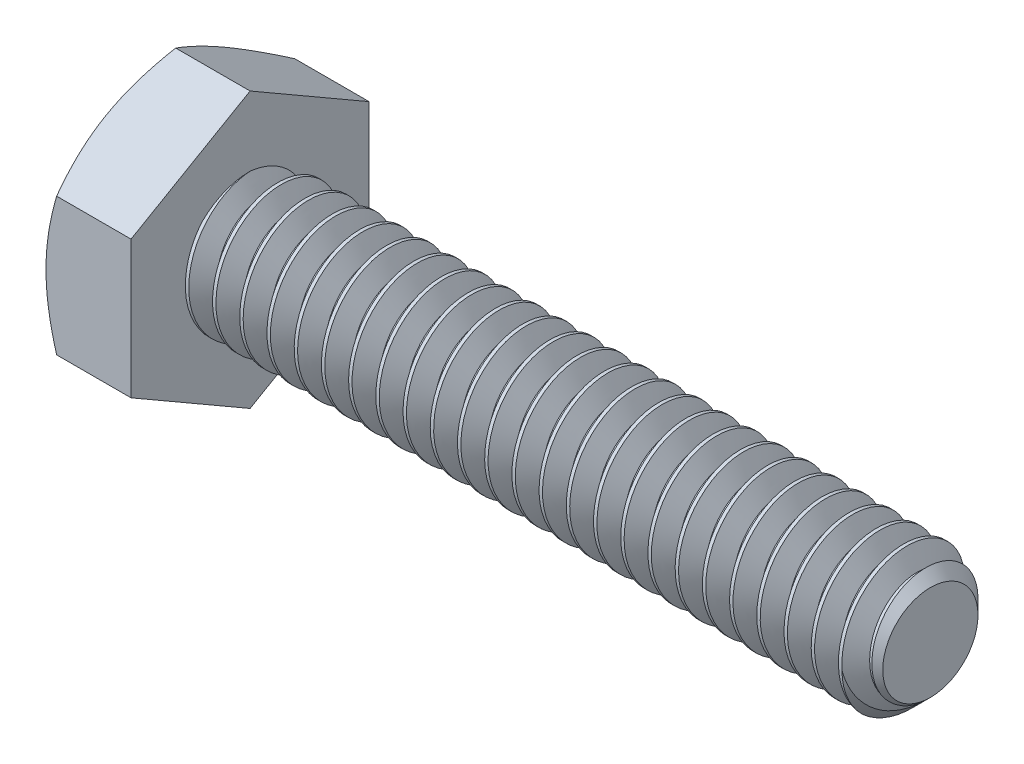
SolidWorks part; units mm, degrees
material "AISI 304"
ref_plane "Front Plane" through (0, 0, 0) normal (0, 0, 1) x (1, 0, 0)
ref_plane "Top Plane" through (0, 0, 0) normal (0, 1, 0) x (1, 0, 0)
ref_plane "Right Plane" through (0, 0, 0) normal (1, 0, 0) x (0, 0, -1)
sketch "Sketch1" plane through (0, 0, 0) normal (0, 0, 1) x (1, 0, 0)
  line L0 (-17.8594, 0) -> (17.8594, 0) construction
  line L1 (17.8594, 3.175) -> (17.8594, -3.175) construction
  line L2 (-13.8906, 5.5562) -> (-13.8906, -5.5562) construction
  line L3 (-17.8594, 5.5562) -> (-17.8594, -5.5562) construction
  point P9 (-13.8906, 0)
  point P10 (13.4144, -3.175)
  dimension "D1" = 4.445
  dimension "Screw Dia" = 6.35
  dimension "Hex" = 11.1125
  dimension "Head Ht" = 3.9688
  dimension "Screw Lenght" = 31.75
ref_plane "Plane2" through (17.8594, 0, 0) normal (1, 0, 0) x (0, 0, -1)
sketch "Sketch5" plane through (17.8594, 0, 0) normal (1, 0, 0) x (0, 0, -1)
  circle A0 centre (0, 0) radius 3.175
extrude "Boss-Extrude3" add sketch "Sketch5" against normal up to vertex (31.75 mm away) up to point (-13.8906, 0, 0)
sketch "Sketch9" plane through (17.8594, 0, 0) normal (1, 0, 0) x (0, 0, -1)
  circle A1 centre (0, 0) radius 3.175
  circle A2 centre (0, 0) radius 3.175
  dimension "D1" = 0
curve "Helix/Spiral1" pitch 1.27 height 33.02 turns 26 parameters "Pitch"=1.27
chamfer "Chamfer1" distance 0.9525 angle 45 1 edges at (17.8594, 0, -3.175)
sketch "Sketch10" plane through (0, 0, 0) normal (0, 0, 1) x (1, 0, 0)
  line L0 (17.8594, 3.175) -> (18.3356, 2.3501)
  line L1 (18.3356, 2.3501) -> (18.4944, 2.3501)
  line L2 (18.4944, 2.3501) -> (18.9706, 3.175)
  line L3 (17.8594, 3.175) -> (18.9706, 3.175)
  line L4 (18.415, 3.175) -> (18.415, 2.3501) construction
  line L5 (18.0975, 2.7626) -> (18.7325, 2.7626) construction
  dimension "D1" = 60
  dimension "D2" = 0.1588
  dimension "D3" = 0.635
sweep "Cut-Sweep1" cut profiles "Sketch10" path "Helix/Spiral1"
sketch "Sketch6" plane through (-13.8906, 0, 0) normal (-1, 0, 0) x (0, 0, 1)
  line L0 (0, 5.5562) -> (0, -5.5562) construction
  line L1 (5.5562, 3.2079) -> (0, 6.4158)
  line L2 (0, 6.4158) -> (-5.5562, 3.2079)
  line L3 (-5.5562, 3.2079) -> (-5.5562, -3.2079)
  line L4 (-5.5562, -3.2079) -> (0, -6.4158)
  line L5 (0, -6.4158) -> (5.5562, -3.2079)
  line L6 (5.5562, -3.2079) -> (5.5562, 3.2079)
  circle A0 centre (0, 0) radius 5.5562 construction
extrude "Boss-Extrude4" add sketch "Sketch6" along normal up to vertex (3.9688 mm away) up to point (-17.8594, -5.5562, 0)
sketch "Sketch7" plane through (-17.8594, 0, 0) normal (-1, 0, 0) x (0, 0, 1)
  circle A0 centre (0, 0) radius 5.5562 construction
  circle A1 centre (0, 0) radius 5.5562
sketch "Sketch8" plane through (-17.8594, 0, 0) normal (-1, 0, 0) x (0, 0, 1)
  circle A0 centre (0, 0) radius 5.5562 construction
  circle A1 centre (0, 0) radius 5.5562
extrude "Cut-Extrude3" cut sketch "Sketch8" against normal through all draft 60 flip side to cut
equation "\"D2@Sketch10\" = \"Pitch@Helix/Spiral1\"*.125"
equation "\"D3@Sketch10\" = \"Pitch@Helix/Spiral1\"*.5"
equation "\"D3@Helix/Spiral1\" = \"Screw Lenght@Sketch1\"+\"Pitch@Helix/Spiral1\""
equation "\"D1@Chamfer1\" = \"Pitch@Helix/Spiral1\"*.75"
equation "\"D1@Sketch1\" = \"Pitch@Helix/Spiral1\"*3.5"
